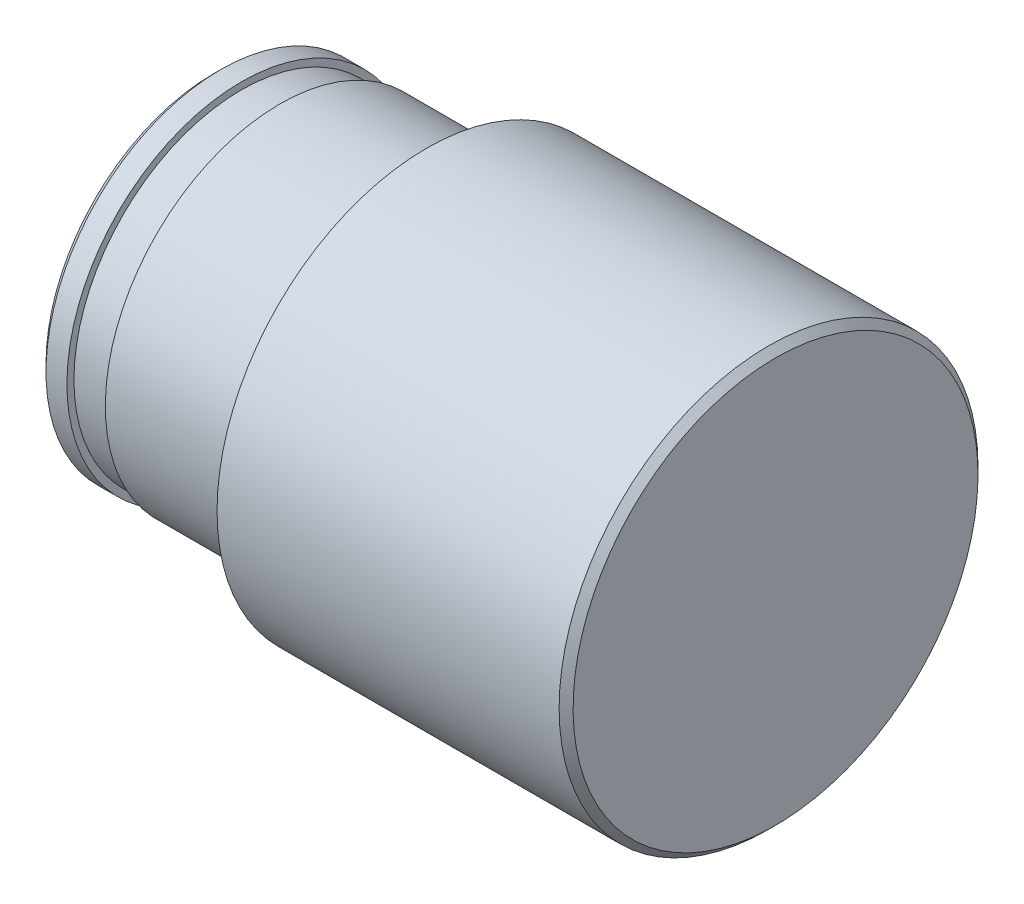
SolidWorks part; units mm, degrees
ref_plane "Vorne" through (0, 0, 0) normal (0, 0, 1) x (1, 0, 0)
ref_plane "Oben" through (0, 0, 0) normal (0, 1, 0) x (1, 0, 0)
ref_plane "Seite" through (0, 0, 0) normal (1, 0, 0) x (0, 0, -1)
sketch "Skizze2" plane through (0, 0, 0) normal (0, 0, 1) x (1, 0, 0)
  line L0 (3.6565, 0) -> (-12.4435, 0)
  line L1 (-12.4435, 0) -> (-12.4435, 5)
  line L2 (-12.4435, 5) -> (-11.6435, 5)
  line L3 (-11.6435, 5) -> (-11.6435, 4.8)
  line L4 (-11.6435, 4.8) -> (-10.5435, 4.8)
  line L5 (-10.5435, 4.8) -> (-10.5435, 5)
  line L6 (-10.5435, 5) -> (-6.3435, 5)
  line L7 (-6.3435, 5) -> (-6.3435, 6)
  line L8 (-6.3435, 6) -> (3.6565, 6)
  line L9 (3.6565, 6) -> (3.6565, 0)
  dimension "D1" = 1.1
  dimension "D2" = 0.2
  dimension "D3" = 0.8
  dimension "D4" = 4.2
  dimension "D5" = 10
  dimension "D6" = 6
  dimension "D7" = 5
revolve "Rotation1" add sketch "Skizze2" angle 360 about L0
chamfer "Fase1" distance 0.2 angle 45 2 edges at (3.6565, 6, 0) (-12.4435, 5, 0)
